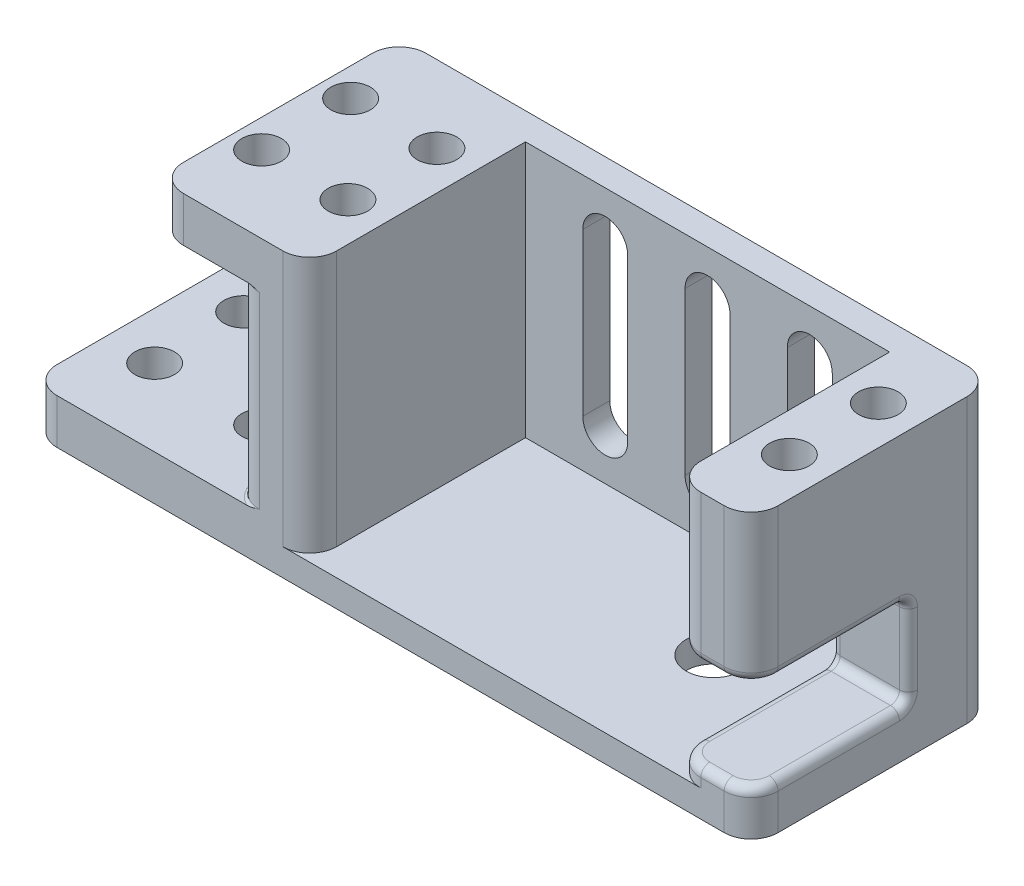
SolidWorks part; units mm, degrees
ref_plane "Front Plane" through (0, 0, 0) normal (0, 0, 1) x (1, 0, 0)
ref_plane "Top Plane" through (0, 0, 0) normal (0, 1, 0) x (1, 0, 0)
ref_plane "Right Plane" through (0, 0, 0) normal (1, 0, 0) x (0, 0, -1)
sketch "Sketch1" plane through (0, 0, 0) normal (0, 1, 0) x (1, 0, 0)
  line L0 (0, 13.5) -> (0, -13.5)
  line L1 (0, -13.5) -> (8.6, -13.5)
  line L3 (0, 13.5) -> (8.6, 13.5)
  line L4 (8.6, -13.5) -> (8.6, 13.5)
  line L5 (0, 0) -> (8.6, 0) construction
  point P0 (0, 0)
  dimension "D1" = 8.6
  dimension "D2" = 27
extrude "Boss-Extrude1" add sketch "Sketch1" along normal blind 31.5
sketch "Sketch2" plane through (8.6, 0, 0) normal (1, 0, 0) x (0, 0, -1)
  line L0 (-13.5, 0) -> (13.5, 0)
  line L1 (-13.5, 0) -> (-13.5, 3)
  line L2 (13.5, 0) -> (13.5, 3)
  line L3 (-13.5, 3) -> (13.5, 3)
  line L4 (-13.5, 31.5) -> (-13.5, 0) construction
  line L5 (13.5, 31.5) -> (13.5, 0) construction
  dimension "D1" = 3
extrude "Boss-Extrude2" add sketch "Sketch2" along normal blind 40.5
sketch "Sketch3" plane through (8.6, 0, 0) normal (1, 0, 0) x (0, 0, -1)
  line L0 (10.5, 31.5) -> (10.5, 3)
  line L1 (10.5, 31.5) -> (13.5, 31.5)
  line L2 (10.5, 3) -> (13.5, 3)
  line L3 (13.5, 31.5) -> (13.5, 3)
  line L4 (0, 31.5) -> (0, 3) construction
  line L5 (-13.5, 31.5) -> (13.5, 31.5) construction
  line L6 (13.5, 3) -> (-13.5, 3) construction
  dimension "D1" = 3
extrude "Boss-Extrude3" add sketch "Sketch3" along normal blind 40.5
sketch "Sketch4" plane through (0, 31.5, 0) normal (0, 1, 0) x (1, 0, 0)
  line L0 (49.1, 13.5) -> (49.1, -13.5)
  line L1 (49.1, 13.5) -> (57.7, 13.5)
  line L2 (49.1, -13.5) -> (57.7, -13.5)
  line L3 (57.7, 13.5) -> (57.7, -13.5)
  line L4 (49.1, 13.5) -> (49.1, 10.5) construction
  line L5 (0, -13.5) -> (8.6, -13.5) construction
  dimension "D1" = 8.6
extrude "Boss-Extrude4" add sketch "Sketch4" against normal blind 31.5
sketch "Sketch15" plane through (0, 0, -10.5) normal (0, 0, 1) x (1, 0, 0)
  line L0 (28.85, 31.5) -> (28.85, 3) construction
  line L1 (49.1, 31.5) -> (8.6, 31.5) construction
  line L2 (49.1, 3) -> (8.6, 3) construction
  line L5 (31.35, 8.25) -> (31.35, 26.25)
  line L7 (26.35, 8.25) -> (26.35, 26.25)
  line L8 (28.85, 17.25) -> (26.35, 26.25) construction
  line L9 (31.35, 26.25) -> (28.85, 17.25) construction
  line L10 (8.6, 17.25) -> (49.1, 17.25) construction
  line L11 (8.6, 31.5) -> (8.6, 3) construction
  line L12 (49.1, 3) -> (49.1, 31.5) construction
  line L13 (42.725, 8.25) -> (42.725, 26.25)
  line L14 (28.85, 17.25) -> (26.35, 8.25) construction
  line L15 (31.35, 8.25) -> (28.85, 17.25) construction
  line L16 (37.725, 8.25) -> (37.725, 26.25)
  line L17 (40.225, 28.75) -> (40.225, 5.75) construction
  line L18 (19.975, 8.25) -> (19.975, 26.25)
  line L19 (14.975, 8.25) -> (14.975, 26.25)
  arc A0 (31.35, 26.25) -> (26.35, 26.25) centre (28.85, 26.25) ccw
  arc A1 (31.35, 8.25) -> (26.35, 8.25) centre (28.85, 8.25) cw
  arc A2 (42.725, 26.25) -> (37.725, 26.25) centre (40.225, 26.25) ccw
  arc A3 (42.725, 8.25) -> (37.725, 8.25) centre (40.225, 8.25) cw
  arc A4 (14.975, 8.25) -> (19.975, 8.25) centre (17.475, 8.25) ccw
  arc A5 (14.975, 26.25) -> (19.975, 26.25) centre (17.475, 26.25) cw
  point P6 (28.85, 17.25)
  dimension "D1" = 18
  dimension "D2" = 5
  dimension "D4" = 11.375
  dimension "D3" = 2
extrude "Cut-Extrude8" cut sketch "Sketch15" against normal blind 10
fillet "Fillet1" radius 3 4 edges at (57.7, 15.75, 13.5) (57.7, 15.75, -13.5) (8.6, 17.25, 13.5) (49.1, 17.25, 13.5)
sketch "Sketch5" plane through (0, 31.5, 0) normal (0, 1, 0) x (1, 0, 0)
  line L0 (0, 0) -> (8.6, 0) construction
  line L1 (8.6, 10.5) -> (8.6, -10.5) construction
  line L2 (0, 13.5) -> (0, -13.5) construction
  line L3 (8.6, 10.5) -> (8.6, -10.5) construction
  line L7 (49.1, 10.5) -> (49.1, -10.5) construction
  circle A0 centre (53.4, 4.95) radius 2.2
  circle A1 centre (53.4, -4.95) radius 2.2
  circle A2 centre (4.3, 4.95) radius 2.2
  circle A3 centre (4.3, -4.95) radius 2.2
  dimension "D1" = 4.4
  dimension "D3" = 4.4
  dimension "D6" = 4.3
  dimension "D7" = 4.3
  dimension "D2" = 9.9
  dimension "D4" = 9.9
  dimension "D5" = 4.95
extrude "Cut-Extrude1" cut sketch "Sketch5" against normal blind 5
sketch "Sketch6" plane through (49.1, 0, 0) normal (-1, 0, 0) x (0, 0, 1)
  line L0 (13.5, 15) -> (13.5, 5)
  line L1 (13.5, 15) -> (-4, 15)
  line L2 (13.5, 5) -> (-4, 5)
  line L3 (-4, 15) -> (-4, 5)
  line L4 (13.5, 3) -> (13.5, 31.5) construction
  line L5 (0, 3) -> (0, 31.5) construction
  line L6 (-10.5, 3) -> (10.5, 3) construction
  line L7 (-10.5, 31.5) -> (10.5, 31.5) construction
  line L8 (-10.5, 3) -> (10.5, 3) construction
  dimension "D1" = 4
  dimension "D2" = 10
  dimension "D3" = 2
extrude "Cut-Extrude2" cut sketch "Sketch6" against normal blind 10
fillet "Fillet3" radius 1 3 edges at (53.4, 15, 13.5) (53.4, 15, -4) (53.4, 5, -4)
sketch "Sketch9" plane through (0, 0, 0) normal (-1, 0, 0) x (0, 0, 1)
  line L4 (-13.5, 31.5) -> (-13.5, 0) construction
  line L5 (13.5, 15.75) -> (-13.5, 15.75) construction
  line L6 (13.5, 31.5) -> (13.5, 0) construction
  line L7 (-13.5, 15.75) -> (13.5, 15.75) construction
  line L8 (-13.5, 31.5) -> (13.5, 31.5)
  line L9 (-13.5, 31.5) -> (-13.5, 26.5)
  line L10 (13.5, 31.5) -> (13.5, 26.5)
  line L11 (-13.5, 26.5) -> (13.5, 26.5)
  line L12 (13.5, 0) -> (13.5, 5)
  line L13 (-13.5, 5) -> (13.5, 5)
  line L14 (-13.5, 0) -> (-13.5, 5)
  line L15 (-13.5, 0) -> (13.5, 0)
  line L16 (-13.5, 31.5) -> (13.5, 31.5) construction
  dimension "D1" = 5
  dimension "D2" = 0
extrude "Boss-Extrude5" add sketch "Sketch9" along normal blind 22.5
sketch "Sketch10" plane through (0, 31.5, 0) normal (0, 1, 0) x (1, 0, 0)
  line L0 (-22.5, 0) -> (0, 0) construction
  line L1 (-22.5, -13.5) -> (-22.5, 13.5) construction
  line L2 (0, 13.5) -> (0, -13.5) construction
  circle A0 centre (-5.3, 4.95) radius 2.2
  circle A1 centre (-5.3, -4.95) radius 2.2
  circle A2 centre (-17.2, -4.95) radius 2.2
  circle A3 centre (-17.2, 4.95) radius 2.2
  dimension "D1" = 4.4
  dimension "D3" = 4.95
  dimension "D4" = 5.3
  dimension "D5" = 11.9
  dimension "D2" = 9.9
extrude "Cut-Extrude5" cut sketch "Sketch10" against normal blind 100
fillet "Fillet4" radius 3 4 edges at (0, 15.75, -13.5) (0, 15.75, 13.5) (-22.5, 2.5, 13.5) (-22.5, 2.5, -13.5)
fillet "Fillet5" radius 0.3 6 edges at (0.8787, 26.5, -12.6213) (0.8787, 26.5, 12.6213) (0.8787, 5, 12.6213) (0.8787, 5, -12.6213) (0, 26.5, 0) (0, 5, 0)
sketch "Sketch12" plane through (0, 31.5, 0) normal (0, 1, 0) x (1, 0, 0)
  line L0 (-22.5, -13.5) -> (5.6, -13.5) construction
  line L1 (-22.5, 13.5) -> (-8.45, 13.5)
  line L2 (-22.5, 13.5) -> (-22.5, -13.5)
  line L3 (-22.5, -13.5) -> (-8.45, -13.5)
  line L4 (-8.45, 13.5) -> (-8.45, -13.5)
extrude "Cut-Extrude6" cut sketch "Sketch12" against normal blind 10
fillet "Fillet6" radius 3 2 edges at (-8.45, 29, -13.5) (-8.45, 29, 13.5)
sketch "Sketch13" plane through (0, 0, 0) normal (0, -1, 0) x (1, 0, 0)
  line L0 (57.7, 0) -> (0, 0) construction
  line L1 (57.7, 10.5) -> (57.7, -10.5) construction
  circle A0 centre (40.02, 0) radius 3.05
  dimension "D1" = 6.1
  dimension "D2" = 17.68
extrude "Cut-Extrude7" cut sketch "Sketch13" against normal blind 10
